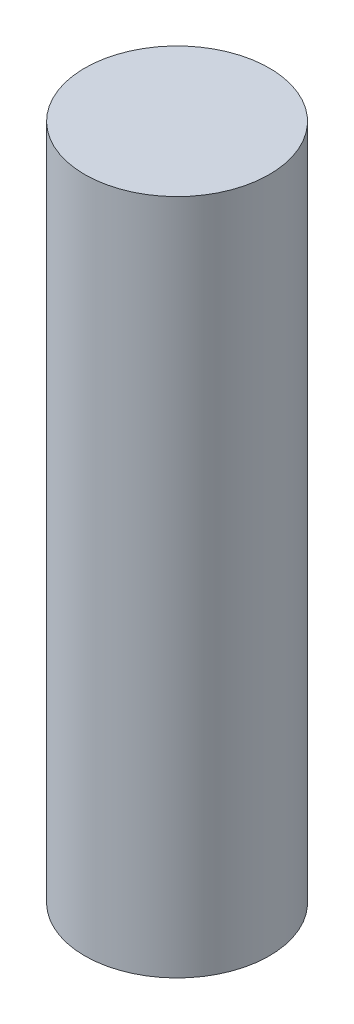
SolidWorks part; units mm, degrees
ref_plane "前视基准面" through (0, 0, 0) normal (0, 0, 1) x (1, 0, 0)
ref_plane "上视基准面" through (0, 0, 0) normal (0, 1, 0) x (1, 0, 0)
ref_plane "右视基准面" through (0, 0, 0) normal (1, 0, 0) x (0, 0, -1)
other "Configuration Table"
sketch "草图1" plane through (0, 0, 0) normal (0, 1, 0) x (1, 0, 0)
  line L5 (241.9495, -230.4137) -> (174.7692, -288.7901) construction
  line L6 (239.2741, -187.6955) -> (283.8763, -239.0243)
  line L10 (239.2741, -187.6955) -> (219.6484, -204.7493)
  line L11 (219.6484, -204.7493) -> (264.2506, -256.0781)
  line L12 (283.8763, -239.0243) -> (264.2506, -256.0781)
  line L13 (400, -400) -> (400, 400)
  line L14 (261.5752, -213.3599) -> (241.9495, -230.4137) construction
  line L15 (219.6484, -204.7493) -> (172.0938, -246.072) construction
  line L16 (152.4681, -263.1258) -> (197.0704, -314.4545)
  line L17 (197.0704, -314.4545) -> (216.6961, -297.4007)
  line L18 (216.6961, -297.4007) -> (172.0938, -246.072)
  line L19 (172.0938, -246.072) -> (152.4681, -263.1258)
  line L20 (162.281, -254.5989) -> (206.8832, -305.9276) construction
  line L21 (172.0938, -246.072) -> (264.2506, -256.0781) construction
  line L22 (218.1722, -251.075) -> (400, -400)
  line L24 (195.8711, -225.4106) -> (0, 0) construction
  line L25 (400, 0) -> (218.1722, -251.075)
  line L38 (0, -440) -> (0, 440) construction
  line L41 (-400, -400) -> (400, -400)
  line L42 (-400, 400) -> (400, 400)
  line L65 (-400, -400) -> (-400, 400)
  line L66 (274.0635, -247.5512) -> (229.4612, -196.2224) construction
  circle A0 centre (0, 0) radius 300
  circle A1 centre (0, 0) radius 150
  point P17 (174.7692, -288.7901)
  point P19 (218.1722, -251.075)
  point P20 (251.7624, -221.8868)
  point P21 (184.5821, -280.2632)
  point P22 (162.281, -254.5989)
  point P25 (229.4612, -196.2224)
  point P49 (-400, 0)
  dimension "D1" = 600
  dimension "D2" = 300
  dimension "D10" = 400
  dimension "D3" = 26
  dimension "D4" = 68
  dimension "D5" = 68
  dimension "D6" = 26
  dimension "D7" = 400
  dimension "D8" = 310
  dimension "D9" = 115
sketch "草图2" plane through (0, 0, 0) normal (0, 1, 0) x (1, 0, 0)
  circle A0 centre (0, 0) radius 150
  dimension "D1" = 300
extrude "凸台-拉伸1" add sketch "草图2" along normal blind 1000 and the other way blind 100
